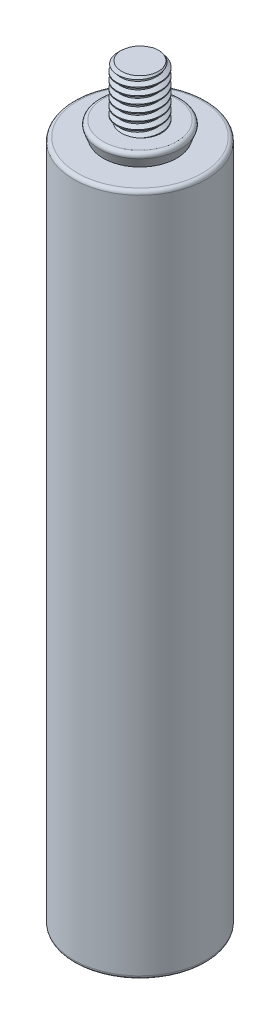
SolidWorks part; units mm, degrees
ref_plane "Ön Düzlem" through (0, 0, 0) normal (0, 0, 1) x (1, 0, 0)
ref_plane "Üst Düzlem" through (0, 0, 0) normal (0, 1, 0) x (1, 0, 0)
ref_plane "Sağ Düzlem" through (0, 0, 0) normal (1, 0, 0) x (0, 0, -1)
sketch "Sketch1" plane through (0, 0, 0) normal (0, 0, 1) x (1, 0, 0)
  line L0 (-9, 80.875) -> (9, 80.875)
  line L1 (9, -87.875) -> (-9, -87.875)
  line L2 (9, -87.875) -> (9, 87.875)
  line L3 (9, 87.875) -> (-9, 87.875)
  line L4 (-9, -87.875) -> (-9, 87.875)
  line L5 (9, -87.875) -> (-9, 87.875) construction
  line L6 (9, 87.875) -> (-9, -87.875) construction
  line L7 (-9, 87.875) -> (-9, 80.875)
  line L8 (-9, -14.125) -> (9, -14.125)
  line L9 (-3, 80.875) -> (3, 80.875)
  line L10 (-3, 80.875) -> (-3, 87.875)
  line L11 (-3, 87.875) -> (3, 87.875)
  line L12 (3, 80.875) -> (3, 87.875)
  line L13 (-3, 80.875) -> (3, 87.875) construction
  line L14 (-3, 87.875) -> (3, 80.875) construction
  line L15 (-9, -87.875) -> (-9, -14.125)
  line L16 (0, 111.54) -> (0, -104.9562)
  line L17 (-3, -87.875) -> (3, -87.875)
  line L18 (-3, -87.875) -> (-3, -12.625)
  line L19 (-3, -12.625) -> (3, -12.625)
  line L20 (3, -87.875) -> (3, -12.625)
  line L21 (-5.7474, 80.875) -> (-5, 78.875)
  line L22 (5, 78.875) -> (-5, 78.875)
  line L24 (5.7474, 80.875) -> (-5.7474, 80.875)
  line L26 (5.0456, 78.9971) -> (-5.7474, 80.875) construction
  line L27 (5.7474, 80.875) -> (-5.0456, 78.9971) construction
  line L28 (5.7474, 80.875) -> (5, 78.875)
  line L29 (-9, 78.875) -> (9, 78.875)
  line L30 (-5.5, -12.625) -> (5.5, -12.625)
  line L31 (3, -12.625) -> (-3, -12.625)
  line L32 (3, -12.625) -> (3, 55.375)
  line L33 (3, 55.375) -> (-3, 55.375)
  line L34 (-3, -12.625) -> (-3, 55.375)
  line L35 (3, -12.625) -> (-3, 55.375) construction
  line L36 (3, 55.375) -> (-3, -12.625) construction
  line L37 (-5.5, -12.625) -> (-5.5, -14.125)
  line L38 (5.5, -12.625) -> (5.5, -14.125)
  point P0 (0, 0)
  point P8 (0, 84.375)
  point P16 (0, 80.875)
  point P22 (0, 79.875)
  point P31 (0, 21.375)
  dimension "D1" = 175.75
  dimension "D2" = 18
  dimension "D3" = 7
  dimension "D4" = 6
  dimension "D5" = 95
  dimension "D6" = 6
  dimension "D7" = 1.5
  dimension "D8" = 68
  dimension "D9" = 5
  dimension "D10" = 1.5
  dimension "D11" = 6
revolve "Revolve1" add sketch "Sketch1" angle 360 about L16 region at (1.5, 84.375, 0) region at (2.6912, 79.8982, 0) region at (5.5027, 36.571, 0)
chamfer "Chamfer1" distance 0.5 1 edges at (0, 87.875, 3)
thread "Thread1" pitch 1 method cut trim with start face yes trim with end face yes profile "Thread Profile1" start angle 0, offset 1, length 8, pitch 1, diameter 6
ref_plane "Plane1" through (-3, 88.375, 0) normal (0, 0, 1) x (-1, 0, 0)
sketch "Thread Profile1" plane through (-3, 88.375, 0) normal (0, 0, 1) x (-1, 0, 0)
  line L0 (0, 0) -> (0, 1) construction
  line L11 (0, 0) -> (0, 0.875)
  line L12 (0, 0.875) -> (-0.5413, 0.5625)
  line L13 (-0.5413, 0.5625) -> (-0.5413, 0.3125)
  line L15 (-0.5413, 0.3125) -> (0, 0)
  line L17 (-0.5413, 0.4375) -> (0, 0.4375) construction
  point P2 (0, 0)
  dimension "Pitch" = 1
  dimension "Profile_Angle" = 60
  dimension "Profile_Land" = 0.25
  dimension "Profile_Height" = 0.5413
fillet "Fillet1" radius 0.5 4 edges at (0, -14.125, 9) (0, 78.875, 9) (0, 80.875, 5.7474) (0, -14.125, 5.5)
